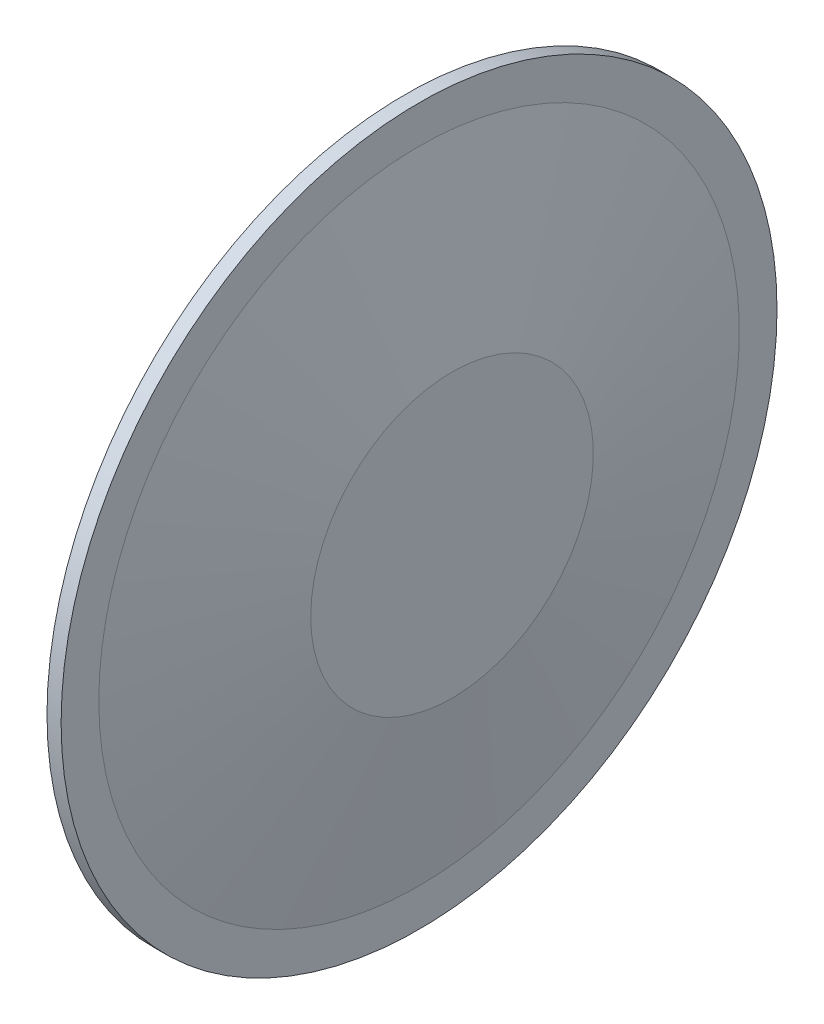
SolidWorks part; units mm, degrees
ref_plane "Front" through (0, 0, 0) normal (0, 0, 1) x (1, 0, 0)
ref_plane "Top" through (0, 0, 0) normal (0, 1, 0) x (1, 0, 0)
ref_plane "Right" through (0, 0, 0) normal (1, 0, 0) x (0, 0, -1)
sketch "Skizze1" plane through (0, 0, 0) normal (0, 0, 1) x (1, 0, 0)
  line L0 (0, 0) -> (27.7436, 0) construction
  line L1 (0, 33.863) -> (0, 38)
  line L2 (0, 38) -> (1.5, 38)
  line L3 (1.5, 38) -> (1.5, 34)
  line L4 (1.5, 34) -> (5, 15)
  line L5 (5, 15) -> (5, 0)
  line L6 (5, 0) -> (3.5, 0)
  line L7 (3.5, 0) -> (3.5, 14.863)
  line L8 (3.5, 14.863) -> (0, 33.863)
  dimension "D1" = 3.5
  dimension "D2" = 1.5
  dimension "D3" = 76
  dimension "D4" = 68
  dimension "D5" = 30
  dimension "D6" = 1.5
  dimension "D7" = 1.5
revolve "Rotation1" add sketch "Skizze1" angle 360 about L0
sketch "Skizze2" plane through (0, 0, 0) normal (1, 0, 0) x (0, 0, -1)
  line L0 (9.525, 0) -> (-9.525, 0) construction
  circle A0 centre (9.525, 0) radius 1.575
  circle A1 centre (-9.525, 0) radius 1.575
  point P6 (0, 0)
  dimension "D1" = 3.15
  dimension "D2" = 19.05
extrude "Aufsatz-Linear austragen1" add sketch "Skizze2" against normal blind 9 from surface starting at face at (3.5, 0, 14.863)
fillet "Verrundung1" radius 1 2 edges at (-5.5, 0, 7.95) (-5.5, 0, -11.1)
fillet "Verrundung2" radius 2.5 2 edges at (3.5, 0, -11.1) (3.5, 0, 7.95)
